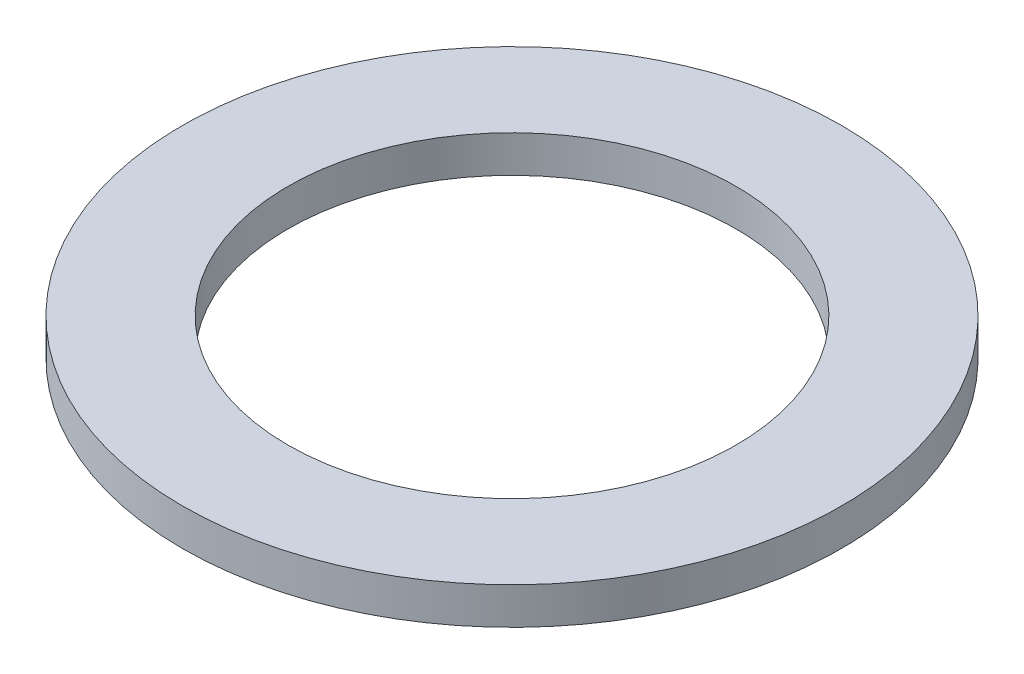
SolidWorks part; units mm, degrees
ref_plane "Front Plane" through (0, 0, 0) normal (0, 0, 1) x (1, 0, 0)
ref_plane "Top Plane" through (0, 0, 0) normal (0, 1, 0) x (1, 0, 0)
ref_plane "Right Plane" through (0, 0, 0) normal (1, 0, 0) x (0, 0, -1)
sketch "Sketch1" plane through (0, 0, 0) normal (0, 1, 0) x (1, 0, 0)
  circle A0 centre (0, 0) radius 62.5
  dimension "FLANGE_OD" = 125
extrude "Boss-Extrude1" add sketch "Sketch1" along normal blind 7
sketch "Sketch2" plane through (0, 0, 0) normal (0, 1, 0) x (1, 0, 0)
  circle A0 centre (0, 0) radius 42.5
  dimension "BORE_D" = 85
extrude "Cut-Extrude1" cut sketch "Sketch2" along normal through all
sketch "Sketch3" plane through (0, 7, 0) normal (0, 1, 0) x (1, 0, 0)
  circle A0 centre (0, 0) radius 23.1988 construction
  circle A1 centre (-23.1988, 0) radius 1.8829
  dimension "BOLT_D" = 3.7658
  dimension "BOLT_PCD" = 46.3976
extrude "Cut-Extrude2" cut sketch "Sketch3" against normal blind 6.0173 rebuild error yes
pattern_circular "CirPattern1" count 6 over 360 rebuild error yes
